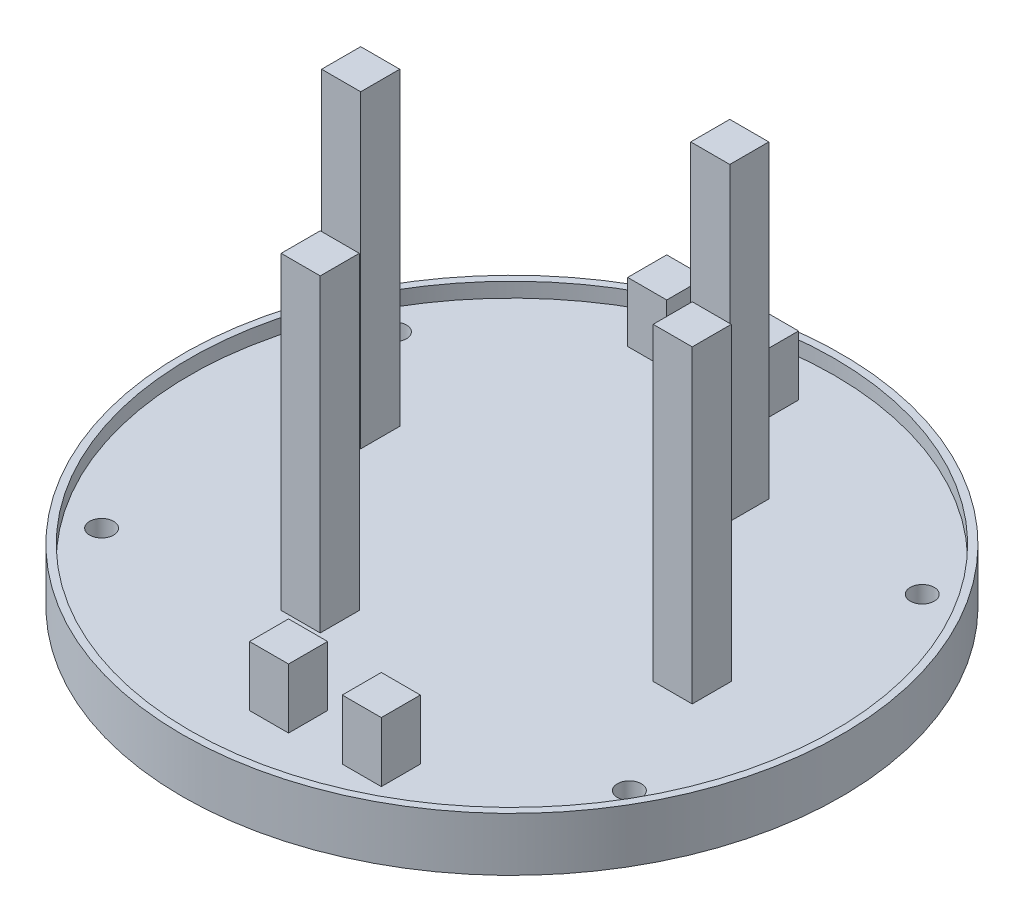
SolidWorks part; units mm, degrees
material "ABS"
ref_plane "Front Plane" through (0, 0, 0) normal (0, 0, 1) x (1, 0, 0)
ref_plane "Top Plane" through (0, 0, 0) normal (0, 1, 0) x (1, 0, 0)
ref_plane "Right Plane" through (0, 0, 0) normal (1, 0, 0) x (0, 0, -1)
sketch "Sketch1" plane through (0, 0, 0) normal (0, 1, 0) x (1, 0, 0)
  circle A0 centre (0, 0) radius 67.5
  dimension "D1" = 135
extrude "Boss-Extrude1" add sketch "Sketch1" along normal blind 11
sketch "Sketch2" plane through (0, 11, 0) normal (0, 1, 0) x (1, 0, 0)
  line L0 (-43.4204, 4.4458) -> (-35.4204, 4.4458)
  line L1 (-35.4204, 4.4458) -> (-35.4204, 12.4458)
  line L2 (-34.4204, -1.6542) -> (-34.4204, 28.3458) construction
  line L3 (-35.4204, 12.4458) -> (-43.4204, 12.4458)
  line L4 (-43.4204, 12.4458) -> (-43.4204, 4.4458)
  line L5 (-33.9004, 14.4458) -> (-38.8004, 14.4458) construction
  line L6 (-26.2429, 49.9457) -> (-18.2429, 49.9457)
  line L7 (-18.2429, 49.9457) -> (-18.2429, 57.9457)
  line L8 (-18.2429, 57.9457) -> (-26.2429, 57.9457)
  line L9 (-26.2429, 57.9457) -> (-26.2429, 49.9457)
  line L10 (-7.2429, 49.9457) -> (0.7571, 49.9458)
  line L11 (0.7571, 49.9458) -> (0.7571, 57.9458)
  line L12 (0.7571, 57.9458) -> (-7.2429, 57.9457)
  line L13 (-7.2429, 57.9457) -> (-7.2429, 49.9457)
  line L14 (7.2671, 29.3513) -> (15.2671, 29.3513)
  line L15 (15.2671, 29.3513) -> (15.2671, 37.3459)
  line L16 (15.2671, 37.3459) -> (7.2671, 37.3459)
  line L17 (7.2671, 37.3459) -> (7.2671, 29.3513)
  line L18 (35.7796, -6.8542) -> (43.7796, -6.8542)
  line L19 (43.7796, -6.8542) -> (43.7796, 1.1458)
  line L20 (43.7796, 1.1458) -> (35.7796, 1.1458)
  line L21 (35.7796, 1.1458) -> (35.7796, -6.8542)
  line L22 (18.6021, -53.3542) -> (26.6021, -53.3541)
  line L23 (26.6021, -53.3541) -> (26.6021, -45.3541)
  line L24 (26.6021, -45.3541) -> (18.6021, -45.3542)
  line L25 (18.6021, -45.3542) -> (18.6021, -53.3542)
  line L26 (-0.3979, -53.3542) -> (7.6021, -53.3542)
  line L27 (7.6021, -53.3542) -> (7.6021, -45.3542)
  line L28 (7.6021, -45.3542) -> (-0.3979, -45.3542)
  line L29 (-0.3979, -45.3542) -> (-0.3979, -53.3542)
  line L30 (-14.9079, -32.3543) -> (-6.9079, -32.3543)
  line L31 (-6.9079, -32.3543) -> (-6.9079, -24.3543)
  line L32 (-6.9079, -24.3543) -> (-14.9079, -24.3543)
  line L33 (-14.9079, -24.3543) -> (-14.9079, -32.3543)
  line L34 (5.267, 48.9458) -> (-29.2429, 48.9457) construction
  line L35 (-29.2429, 46.9458) -> (-29.2429, 42.4458) construction
  line L36 (-4.9078, -44.3542) -> (29.6021, -44.3541) construction
  line L37 (29.6021, -42.3542) -> (29.6021, -37.8542) construction
  line L39 (-5.9079, -30.6042) -> (-5.9079, -32.3542) construction
  line L41 (34.7796, 6.2458) -> (34.7796, -23.7542) construction
  line L42 (34.2596, -9.8542) -> (39.1596, -9.8542) construction
  line L43 (-29.2428, 33.9458) -> (5.2671, 33.9459) construction
  line L44 (29.602, -29.3542) -> (-4.9079, -29.3543) construction
  circle A0 centre (0, 0) radius 66
  circle A1 centre (0, 0) radius 67.5 construction
  circle A2 centre (-39.4204, 8.4458) radius 3.2385 construction
  circle A3 centre (-22.2429, 53.9457) radius 3.2385 construction
  circle A4 centre (-3.2429, 53.9458) radius 3.2385 construction
  circle A5 centre (11.2671, 33.3459) radius 3.2385 construction
  circle A6 centre (39.7796, -2.8542) radius 3.2385 construction
  circle A7 centre (22.6021, -49.3541) radius 3.2385 construction
  circle A8 centre (3.6021, -49.3542) radius 3.2385 construction
  circle A9 centre (-10.9079, -28.3543) radius 3.2385 construction
  dimension "D1" = 1.5
  dimension "D8" = 4
  dimension "D2" = 8
  dimension "D3" = 8
  dimension "D4" = 8
  dimension "D5" = 8
  dimension "D6" = 1
  dimension "D7" = 2
  dimension "D9" = 4
  dimension "D10" = 1
  dimension "D11" = 3
  dimension "D12" = 8
  dimension "D13" = 8
  dimension "D14" = 8
  dimension "D15" = 8
  dimension "D16" = 4
  dimension "D17" = 4
  dimension "D18" = 8
  dimension "D19" = 8
  dimension "D20" = 8
  dimension "D21" = 8
  dimension "D22" = 4
  dimension "D23" = 4
  dimension "D24" = 1
  dimension "D25" = 11
  dimension "D26" = 8
  dimension "D27" = 8
  dimension "D28" = 8
  dimension "D29" = 8
  dimension "D30" = 4
  dimension "D31" = 4
  dimension "D32" = 1
  dimension "D33" = 8
  dimension "D34" = 8
  dimension "D35" = 8
  dimension "D36" = 8
  dimension "D37" = 4
  dimension "D38" = 4
  dimension "D39" = 3
  dimension "D40" = 1
  dimension "D41" = 11
  dimension "D42" = 8
  dimension "D43" = 8
  dimension "D44" = 8
  dimension "D45" = 8
  dimension "D46" = 4
  dimension "D47" = 4
  dimension "D48" = 1
  dimension "D49" = 8
  dimension "D50" = 8
  dimension "D51" = 8
  dimension "D52" = 8
  dimension "D53" = 4
  dimension "D54" = 4
  dimension "D55" = 1
  dimension "D56" = 3
  dimension "D57" = 1
  dimension "D58" = 4
  dimension "D59" = 4
  dimension "D60" = 8
  dimension "D61" = 3.4
  dimension "D62" = 3
extrude "Cut-Extrude1" cut sketch "Sketch2" against normal blind 3
extrude "Cut-Extrude2" cut sketch "Sketch2<2>" along normal blind 2 from surface starting at face at (0, 0, 67.5)
sketch "Sketch2<2>" plane through (0, 11, 0) normal (0, 1, 0) x (1, 0, 0) same geometry as "Sketch2"
sketch "ref sketch for holes" plane through (0, 2, 0) normal (0, -1, 0) x (1, 0, 0)
  line L0 (52.7141, 28.6571) -> (47.8775, -36.1627) construction
  line L1 (47.8775, -36.1627) -> (-52.7141, -28.6571) construction
  line L2 (-52.7141, -28.6571) -> (-47.8775, 36.1627) construction
  line L3 (-47.8775, 36.1627) -> (52.7141, 28.6571) construction
hole_wizard "CSK for #8 Flat Head Socket Cap Screw1" positions "Sketch5" profile "Sketch4" countersink size "#8" standard "ANSI Inch" end condition through all
sketch "Sketch5" plane through (0, 2, 0) normal (0, -1, 0) x (-1, 0, 0)
  point P0 (52.7141, 28.6571)
  point P3 (-47.8775, 36.1627)
  point P6 (-52.7141, -28.6571)
  point P9 (47.8775, -36.1627)
sketch "Sketch4" plane through (-52.7141, 2, -28.6571) normal (1, 0, 0) x (0, 0, -1)
  line L0 (0, 0) -> (0, 9)
  line L1 (0, 9) -> (2.4574, 9)
  line L2 (2.4574, 9) -> (2.4574, 2.4179)
  line L3 (2.4574, 2.4179) -> (4.5593, 0)
  line L5 (4.5593, 0) -> (0, 0)
  line L6 (-2.4574, 2.4179) -> (-4.5593, 0) construction
  line L11 (0, -6.35) -> (0, 107.95) construction
  dimension "Thru Hole Dia." = 4.9149
  dimension "Thru Hole Depth" = 9
  dimension "Near C'Sink Dia." = 9.1186
  dimension "Near C'Sink Angle" = 82
sketch "Sketch10" [suppressed] plane through (0, 8, 0) normal (0, 1, 0) x (1, 0, 0)
  line L0 (26.6021, -53.3541) -> (26.6021, -45.3541) construction
  line L1 (26.6021, -45.3541) -> (18.6021, -45.3542) construction
  line L2 (18.6021, -45.3542) -> (18.6021, -53.3542) construction
  line L3 (-0.3979, -45.3542) -> (-0.3979, -53.3542) construction
  line L4 (26.6021, -45.3541) -> (18.6021, -45.3542)
  line L5 (26.6021, -53.3541) -> (26.6021, -45.3541)
  line L6 (18.6021, -53.3542) -> (26.6021, -53.3541)
  line L7 (18.6021, -45.3542) -> (18.6021, -53.3542)
  line L8 (26.6021, -45.3541) -> (18.6021, -45.3542)
  line L9 (26.6021, -53.3541) -> (26.6021, -45.3541)
  line L10 (18.6021, -53.3542) -> (26.6021, -53.3541)
  line L11 (18.6021, -45.3542) -> (18.6021, -53.3542)
  line L12 (7.6021, -45.3542) -> (-0.3979, -45.3542)
  line L13 (7.6021, -53.3542) -> (7.6021, -45.3542)
  line L14 (-0.3979, -53.3542) -> (7.6021, -53.3542)
  line L15 (-0.3979, -45.3542) -> (-0.3979, -53.3542)
  line L16 (7.6021, -45.3542) -> (-0.3979, -45.3542)
  line L17 (7.6021, -53.3542) -> (7.6021, -45.3542)
  line L18 (-0.3979, -53.3542) -> (7.6021, -53.3542)
  line L19 (-0.3979, -45.3542) -> (-0.3979, -53.3542)
  line L20 (43.7796, 1.1458) -> (35.7796, 1.1458)
  line L21 (43.7796, -6.8542) -> (43.7796, 1.1458)
  line L22 (35.7796, -6.8542) -> (43.7796, -6.8542)
  line L23 (35.7796, 1.1458) -> (35.7796, -6.8542)
  line L24 (43.7796, 1.1458) -> (35.7796, 1.1458)
  line L25 (43.7796, -6.8542) -> (43.7796, 1.1458)
  line L26 (35.7796, -6.8542) -> (43.7796, -6.8542)
  line L27 (35.7796, 1.1458) -> (35.7796, -6.8542)
  line L28 (-6.9079, -24.3543) -> (-14.9079, -24.3543)
  line L29 (-6.9079, -32.3543) -> (-6.9079, -24.3543)
  line L30 (-14.9079, -32.3543) -> (-6.9079, -32.3543)
  line L31 (-14.9079, -24.3543) -> (-14.9079, -32.3543)
  line L32 (-6.9079, -24.3543) -> (-14.9079, -24.3543)
  line L33 (-6.9079, -32.3543) -> (-6.9079, -24.3543)
  line L34 (-14.9079, -32.3543) -> (-6.9079, -32.3543)
  line L35 (-14.9079, -24.3543) -> (-14.9079, -32.3543)
  line L36 (7.6021, -45.3542) -> (-0.3979, -45.3542) construction
  line L37 (35.7796, 1.1458) -> (35.7796, -6.8542) construction
  line L38 (43.7796, -6.8542) -> (43.7796, 1.1458) construction
  line L39 (43.7796, 1.1458) -> (35.7796, 1.1458) construction
  line L40 (-14.9079, -24.3543) -> (-14.9079, -32.3543) construction
  line L41 (-6.9079, -32.3543) -> (-6.9079, -24.3543) construction
  line L42 (-6.9079, -24.3543) -> (-14.9079, -24.3543) construction
  line L43 (15.2671, 29.3513) -> (15.2671, 37.3459) construction
  line L44 (26.6021, -53.3541) -> (26.6021, -45.3541)
  line L45 (26.6021, -45.3541) -> (18.6021, -45.3542)
  line L46 (18.6021, -45.3542) -> (18.6021, -53.3542)
  line L47 (-0.3979, -45.3542) -> (-0.3979, -53.3542)
  line L48 (7.6021, -45.3542) -> (-0.3979, -45.3542)
  line L49 (35.7796, 1.1458) -> (35.7796, -6.8542)
  line L50 (43.7796, -6.8542) -> (43.7796, 1.1458)
  line L51 (43.7796, 1.1458) -> (35.7796, 1.1458)
  line L52 (-14.9079, -24.3543) -> (-14.9079, -32.3543)
  line L53 (-6.9079, -32.3543) -> (-6.9079, -24.3543)
  line L54 (-6.9079, -24.3543) -> (-14.9079, -24.3543)
  line L55 (15.2671, 29.3513) -> (15.2671, 37.3459)
  dimension "D1" = 0
  dimension "D2" = 0
  dimension "D3" = 0
  dimension "D4" = 0
sketch "Sketch11" plane through (0, 8, 0) normal (0, 1, 0) x (1, 0, 0)
  line L4 (-43.4204, 4.4458) -> (-35.4204, 4.4458)
  line L5 (-35.4204, 4.4458) -> (-35.4204, 12.4458)
  line L6 (-35.4204, 12.4458) -> (-43.4204, 12.4458)
  line L7 (-43.4204, 12.4458) -> (-43.4204, 4.4458)
  line L8 (-43.4204, 4.4458) -> (-35.4204, 4.4458)
  line L9 (-35.4204, 4.4458) -> (-35.4204, 12.4458)
  line L10 (-35.4204, 12.4458) -> (-43.4204, 12.4458)
  line L11 (-43.4204, 12.4458) -> (-43.4204, 4.4458)
  line L12 (7.2671, 29.3513) -> (15.2671, 29.3513)
  line L13 (15.2671, 29.3513) -> (15.2671, 37.3459)
  line L14 (15.2671, 37.3459) -> (7.2671, 37.3459)
  line L15 (7.2671, 37.3459) -> (7.2671, 29.3513)
  line L16 (7.2671, 29.3513) -> (15.2671, 29.3513)
  line L17 (15.2671, 29.3513) -> (15.2671, 37.3459)
  line L18 (15.2671, 37.3459) -> (7.2671, 37.3459)
  line L19 (7.2671, 37.3459) -> (7.2671, 29.3513)
  line L20 (-7.2429, 49.9457) -> (0.7571, 49.9458)
  line L21 (0.7571, 49.9458) -> (0.7571, 57.9458)
  line L22 (0.7571, 57.9458) -> (-7.2429, 57.9457)
  line L23 (-7.2429, 57.9457) -> (-7.2429, 49.9457)
  line L24 (-7.2429, 49.9457) -> (0.7571, 49.9458)
  line L25 (0.7571, 49.9458) -> (0.7571, 57.9458)
  line L26 (0.7571, 57.9458) -> (-7.2429, 57.9457)
  line L27 (-7.2429, 57.9457) -> (-7.2429, 49.9457)
  line L28 (-18.2429, 49.9457) -> (-18.2429, 57.9457)
  line L29 (-18.2429, 57.9457) -> (-26.2429, 57.9457)
  line L30 (-26.2429, 57.9457) -> (-26.2429, 49.9457)
  line L31 (-26.2429, 49.9457) -> (-18.2429, 49.9457)
  line L32 (-18.2429, 49.9457) -> (-18.2429, 57.9457)
  line L33 (-18.2429, 57.9457) -> (-26.2429, 57.9457)
  line L34 (-26.2429, 57.9457) -> (-26.2429, 49.9457)
  line L35 (-26.2429, 49.9457) -> (-18.2429, 49.9457)
  line L36 (18.6021, -53.3542) -> (26.6021, -53.3541)
  line L37 (26.6021, -53.3541) -> (26.6021, -45.3541)
  line L38 (26.6021, -45.3541) -> (18.6021, -45.3542)
  line L39 (18.6021, -45.3542) -> (18.6021, -53.3542)
  line L40 (18.6021, -53.3542) -> (26.6021, -53.3541)
  line L41 (26.6021, -53.3541) -> (26.6021, -45.3541)
  line L42 (26.6021, -45.3541) -> (18.6021, -45.3542)
  line L43 (18.6021, -45.3542) -> (18.6021, -53.3542)
  line L44 (35.7796, -6.8542) -> (43.7796, -6.8542)
  line L45 (43.7796, -6.8542) -> (43.7796, 1.1458)
  line L46 (43.7796, 1.1458) -> (35.7796, 1.1458)
  line L47 (35.7796, 1.1458) -> (35.7796, -6.8542)
  line L48 (35.7796, -6.8542) -> (43.7796, -6.8542)
  line L49 (43.7796, -6.8542) -> (43.7796, 1.1458)
  line L50 (43.7796, 1.1458) -> (35.7796, 1.1458)
  line L51 (35.7796, 1.1458) -> (35.7796, -6.8542)
  line L52 (-14.9079, -32.3543) -> (-6.9079, -32.3543)
  line L53 (-6.9079, -32.3543) -> (-6.9079, -24.3543)
  line L54 (-6.9079, -24.3543) -> (-14.9079, -24.3543)
  line L55 (-14.9079, -24.3543) -> (-14.9079, -32.3543)
  line L56 (-14.9079, -32.3543) -> (-6.9079, -32.3543)
  line L57 (-6.9079, -32.3543) -> (-6.9079, -24.3543)
  line L58 (-6.9079, -24.3543) -> (-14.9079, -24.3543)
  line L59 (-14.9079, -24.3543) -> (-14.9079, -32.3543)
  line L60 (7.6021, -45.3542) -> (-0.3979, -45.3542)
  line L61 (7.6021, -53.3542) -> (7.6021, -45.3542)
  line L62 (-0.3979, -53.3542) -> (7.6021, -53.3542)
  line L63 (-0.3979, -45.3542) -> (-0.3979, -53.3542)
  line L64 (7.6021, -45.3542) -> (-0.3979, -45.3542)
  line L65 (7.6021, -53.3542) -> (7.6021, -45.3542)
  line L66 (-0.3979, -53.3542) -> (7.6021, -53.3542)
  line L67 (-0.3979, -45.3542) -> (-0.3979, -53.3542)
  circle A1 centre (0, 0) radius 66
  circle A2 centre (0, 0) radius 66
  line M50 (7.2671, 37.3459) -> (15.2671, 37.3459)
  line M51 (15.2671, 37.3459) -> (15.2671, 29.3513)
  line M52 (15.2671, 29.3513) -> (7.2671, 29.3513)
  line M53 (7.2671, 29.3513) -> (7.2671, 37.3459)
  dimension "D1" = 0
  dimension "D2" = 0
  dimension "D3" = 0
  dimension "D4" = 0
  dimension "D5" = 0
  dimension "D6" = 0
  dimension "D7" = 0
  dimension "D8" = 0
  dimension "D9" = 0
extrude "Boss-Extrude4" add sketch "Sketch11" along normal blind 63.34 separate body contours M50 M53 M52 M51 | L50 L51 L48 L49 | L59 L56 L57 L58 | L11 L8 L9 L10 region at (11.2671, 8, -33.3486)
sketch "Sketch12" plane through (0, 8, 0) normal (0, 1, 0) x (1, 0, 0)
  line L0 (18.6021, -53.3542) -> (18.6021, -45.3542)
  line L1 (18.6021, -45.3542) -> (18.6021, -53.3542) construction
  line L2 (18.6021, -53.3542) -> (26.6021, -53.3541) construction
  line L3 (18.6021, -45.3542) -> (26.6021, -45.3541)
  line L4 (26.6021, -45.3541) -> (18.6021, -45.3542) construction
  line L5 (26.6021, -53.3541) -> (26.6021, -45.3541) construction
  line L6 (26.6021, -45.3541) -> (26.6021, -53.3541)
  line L7 (26.6021, -53.3541) -> (18.6021, -53.3542)
  line L8 (7.6021, -53.3542) -> (-0.3979, -53.3542)
  line L9 (7.6021, -53.3542) -> (7.6021, -45.3542) construction
  line L10 (-0.3979, -53.3542) -> (7.6021, -53.3542) construction
  line L11 (-0.3979, -45.3542) -> (-0.3979, -53.3542) construction
  line L12 (-0.3979, -53.3542) -> (-0.3979, -45.3542)
  line L13 (7.6021, -45.3542) -> (-0.3979, -45.3542) construction
  line L14 (-0.3979, -45.3542) -> (7.6021, -45.3542)
  line L15 (7.6021, -45.3542) -> (7.6021, -53.3542)
  line L16 (0.7571, 57.9458) -> (-7.2429, 57.9457)
  line L17 (0.7571, 57.9458) -> (-7.2429, 57.9457) construction
  line L18 (0.7571, 49.9458) -> (0.7571, 57.9458) construction
  line L19 (-7.2429, 57.9457) -> (-7.2429, 49.9457)
  line L20 (-7.2429, 49.9457) -> (0.7571, 49.9458) construction
  line L21 (-7.2429, 57.9457) -> (-7.2429, 49.9457) construction
  line L22 (-7.2429, 49.9457) -> (0.7571, 49.9458)
  line L23 (0.7571, 49.9458) -> (0.7571, 57.9458)
  line L24 (-18.2429, 57.9457) -> (-26.2429, 57.9457)
  line L25 (-18.2429, 49.9457) -> (-18.2429, 57.9457) construction
  line L26 (-18.2429, 57.9457) -> (-26.2429, 57.9457) construction
  line L27 (-26.2429, 57.9457) -> (-26.2429, 49.9457)
  line L28 (-26.2429, 49.9457) -> (-18.2429, 49.9457) construction
  line L29 (-26.2429, 49.9457) -> (-18.2429, 49.9457)
  line L30 (-18.2429, 49.9457) -> (-18.2429, 57.9457)
  line L32 (18.6021, -46.5243) -> (18.6021, -45.3542)
  line L34 (7.6021, -46.5243) -> (7.6021, -45.3542)
extrude "Boss-Extrude5" add sketch "Sketch12" along normal blind 12.25 contours L15 L8 L12 L14 | L3 L6 L7 L0 | L23 L16 L19 L22 | L30 L24 L27 L29
